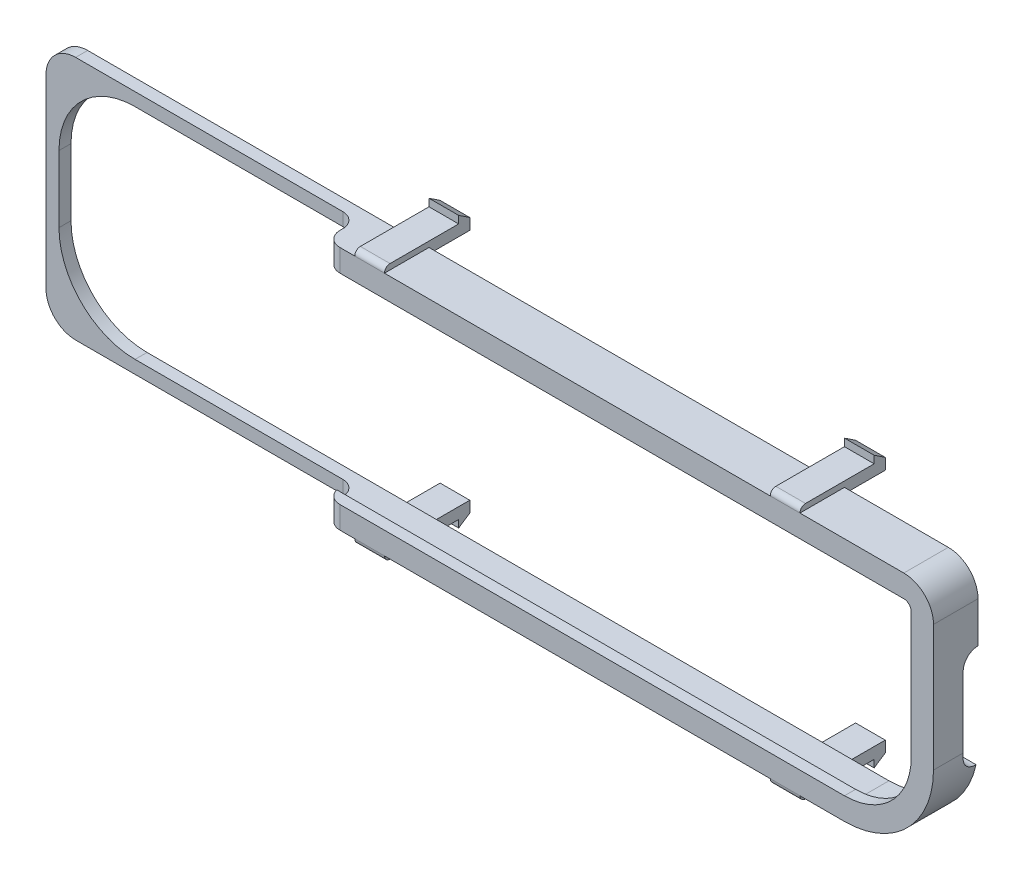
SolidWorks part; units mm, degrees
ref_plane "Front" through (0, 0, 0) normal (0, 0, 1) x (1, 0, 0)
ref_plane "Top" through (0, 0, 0) normal (0, 1, 0) x (1, 0, 0)
ref_plane "Right" through (0, 0, 0) normal (1, 0, 0) x (0, 0, -1)
ref_plane "Plane1 - PCB bottom plane" through (0, 0, 0) normal (0, 0, 1) x (1, 0, 0)
sketch "Sketch2 - footprint" plane through (0, 0, 0) normal (0, 0, 1) x (1, 0, 0)
  line L1 (10, 14.5) -> (118, 14.5) construction
  line L2 (0, 4.5) -> (0, -4.5) construction
  line L3 (10, -14.5) -> (110, -14.5) construction
  line L4 (120, 12.5) -> (120, -4.5) construction
  arc A0 (110, -14.5) -> (120, -4.5) centre (110, -4.5) ccw construction
  arc A1 (120, 12.5) -> (118, 14.5) centre (118, 12.5) ccw construction
  arc A2 (10, -14.5) -> (0, -4.5) centre (10, -4.5) cw construction
  arc A3 (10, 14.5) -> (0, 4.5) centre (10, 4.5) ccw construction
  point P4 (0, 0)
  point P10 (120, 14.5)
  point P13 (0, -14.5)
  point P16 (0, 14.5)
  dimension "D3" = 10
  dimension "D4" = 2
  dimension "D1" = 29
  dimension "D2" = 120
sketch "Sketch3" plane through (0, 0, 0) normal (0, 0, 1) x (1, 0, 0)
  line L33 (118, 14.75) -> (10, 14.75)
  line L34 (120.25, -4.5) -> (120.25, 12.5)
  line L35 (10, -14.75) -> (110, -14.75)
  line L36 (-0.25, 4.5) -> (-0.25, -4.5)
  line L37 (118, 14.75) -> (10, 14.75)
  line L38 (120.25, -4.5) -> (120.25, 12.5)
  line L39 (10, -14.75) -> (110, -14.75)
  line L40 (-0.25, 4.5) -> (-0.25, -4.5)
  line L45 (122, -4.5) -> (122, 12.5)
  line L46 (10, -16.5) -> (110, -16.5)
  line L47 (-2, 4.5) -> (-2, -4.5)
  line L48 (118, 16.5) -> (10, 16.5)
  line L49 (122, -4.5) -> (122, 12.5)
  line L50 (10, -16.5) -> (110, -16.5)
  line L51 (-2, 4.5) -> (-2, -4.5)
  line L52 (118, 16.5) -> (10, 16.5)
  arc A33 (120.25, 12.5) -> (118, 14.75) centre (118, 12.5) ccw
  arc A34 (110, -14.75) -> (120.25, -4.5) centre (110, -4.5) ccw
  arc A35 (-0.25, -4.5) -> (10, -14.75) centre (10, -4.5) ccw
  arc A36 (10, 14.75) -> (-0.25, 4.5) centre (10, 4.5) ccw
  arc A37 (120.25, 12.5) -> (118, 14.75) centre (118, 12.5) ccw
  arc A38 (110, -14.75) -> (120.25, -4.5) centre (110, -4.5) ccw
  arc A39 (-0.25, -4.5) -> (10, -14.75) centre (10, -4.5) ccw
  arc A40 (10, 14.75) -> (-0.25, 4.5) centre (10, 4.5) ccw
  arc A45 (122, 12.5) -> (118, 16.5) centre (118, 12.5) ccw
  arc A46 (110, -16.5) -> (122, -4.5) centre (110, -4.5) ccw
  arc A47 (-2, -4.5) -> (10, -16.5) centre (10, -4.5) ccw
  arc A48 (10, 16.5) -> (-2, 4.5) centre (10, 4.5) ccw
  arc A49 (122, 12.5) -> (118, 16.5) centre (118, 12.5) ccw
  arc A50 (110, -16.5) -> (122, -4.5) centre (110, -4.5) ccw
  arc A51 (-2, -4.5) -> (10, -16.5) centre (10, -4.5) ccw
  arc A52 (10, 16.5) -> (-2, 4.5) centre (10, 4.5) ccw
  dimension "D1" = 0.25
  dimension "D2" = 2
extrude "Boss-Extrude2 - thickness of TC + PCB" add sketch "Sketch3" along normal blind 4.5
sketch "Sketch4" plane through (0, 0, 4.5) normal (0, 0, 1) x (1, 0, 0)
  line L0 (40, 14.5) -> (118, 14.5) construction
  line L1 (10, 14.5) -> (118, 14.5) construction
  line L2 (40, -14.5) -> (110, -14.5) construction
  line L3 (10, -14.5) -> (110, -14.5) construction
  line L4 (120, 12.5) -> (120, -4.5) construction
  line L5 (120, 12.5) -> (120, -4.5) construction
  line L6 (40, 13.5) -> (118, 13.5)
  line L7 (119, 12.5) -> (119, -4.5)
  line L8 (40, -13.5) -> (110, -13.5)
  line L9 (40, 13.5) -> (40, 16.5)
  line L10 (118, 16.5) -> (10, 16.5) construction
  line L11 (40, 16.5) -> (118, 16.5)
  line L12 (40, -13.5) -> (40, -16.5)
  line L13 (10, -16.5) -> (110, -16.5) construction
  line L14 (40, -16.5) -> (110, -16.5)
  line L15 (122, -4.5) -> (122, 12.5) construction
  line L16 (122, -4.5) -> (122, 12.5)
  arc A0 (110, -14.5) -> (120, -4.5) centre (110, -4.5) ccw construction
  arc A1 (120, 12.5) -> (118, 14.5) centre (118, 12.5) ccw construction
  arc A2 (110, -14.5) -> (120, -4.5) centre (110, -4.5) ccw construction
  arc A3 (120, 12.5) -> (118, 14.5) centre (118, 12.5) ccw construction
  arc A4 (119, 12.5) -> (118, 13.5) centre (118, 12.5) ccw
  arc A5 (110, -13.5) -> (119, -4.5) centre (110, -4.5) ccw
  arc A6 (110, -16.5) -> (122, -4.5) centre (110, -4.5) ccw construction
  arc A7 (122, 12.5) -> (118, 16.5) centre (118, 12.5) ccw construction
  arc A8 (110, -16.5) -> (122, -4.5) centre (110, -4.5) ccw
  arc A9 (122, 12.5) -> (118, 16.5) centre (118, 12.5) ccw
  dimension "D1" = 80
  dimension "D2" = 1
extrude "Boss-Extrude3 - retaining top" add sketch "Sketch4" along normal blind 1.5
sketch "Sketch5" plane through (0, 0, 4.5) normal (0, 0, 1) x (1, 0, 0)
  line L8 (40, -16.5) -> (40, -14.75)
  line L9 (40, -14.75) -> (10, -14.75)
  line L10 (-0.25, -4.5) -> (-0.25, 4.5)
  line L11 (10, 14.75) -> (40, 14.75)
  line L12 (40, 14.75) -> (40, 16.5)
  line L13 (40, 16.5) -> (10, 16.5)
  line L14 (-2, 4.5) -> (-2, -4.5)
  line L15 (10, -16.5) -> (40, -16.5)
  line L16 (40, -16.5) -> (40, -14.75)
  line L17 (40, -14.75) -> (10, -14.75)
  line L18 (-0.25, -4.5) -> (-0.25, 4.5)
  line L19 (10, 14.75) -> (40, 14.75)
  line L20 (40, 14.75) -> (40, 16.5)
  line L21 (40, 16.5) -> (10, 16.5)
  line L22 (-2, 4.5) -> (-2, -4.5)
  line L23 (10, -16.5) -> (40, -16.5)
  arc A4 (-0.25, -4.5) -> (10, -14.75) centre (10, -4.5) ccw
  arc A5 (10, 14.75) -> (-0.25, 4.5) centre (10, 4.5) ccw
  arc A6 (10, 16.5) -> (-2, 4.5) centre (10, 4.5) ccw
  arc A7 (-2, -4.5) -> (10, -16.5) centre (10, -4.5) ccw
  arc A8 (-0.25, -4.5) -> (10, -14.75) centre (10, -4.5) ccw
  arc A9 (10, 14.75) -> (-0.25, 4.5) centre (10, 4.5) ccw
  arc A10 (10, 16.5) -> (-2, 4.5) centre (10, 4.5) ccw
  arc A11 (-2, -4.5) -> (10, -16.5) centre (10, -4.5) ccw
  dimension "D1" = 0
extrude "Cut-Extrude1 - exposed TC front" cut sketch "Sketch5" against normal blind 2.881
fillet "Fillet1" radius 2 4 edges at (40, 15, 6) (40, 15.625, 1.619) (40, -15, 6) (40, -15.625, 1.619)
sketch "Sketch6" plane through (0, 0, 1.619) normal (0, 0, 1) x (1, 0, 0)
  line L0 (-0.25, -4.5) -> (-0.25, 4.5) construction
  line L1 (-0.25, 3) -> (-2, 3)
  line L2 (-0.25, 3) -> (-0.25, -3)
  line L3 (-0.25, -3) -> (-2, -3)
  line L4 (-2, 3) -> (-2, -3)
  line L5 (-2, 4.5) -> (-2, -4.5) construction
  point P9 (-0.25, 0)
  dimension "D1" = 6
extrude "Boss-Extrude4 - front lip" [suppressed] add sketch "Sketch6" along normal blind 1
fillet "Fillet2" [suppressed] radius 1
sketch "Sketch7" plane through (122, 0, 0) normal (1, 0, 0) x (0, 0, -1)
  line L0 (0, -4.5) -> (0, 12.5) construction
  line L1 (0, -7) -> (-2, -7)
  line L2 (0, -7) -> (0, 7)
  line L3 (0, 7) -> (-2, 7)
  line L4 (-2, -7) -> (-2, 7)
  point P7 (0, 0)
  dimension "D1" = 14
  dimension "D2" = 2
extrude "Cut-Extrude1 - USBC cutout" cut sketch "Sketch7" against normal blind 5
fillet "Fillet3" radius 2 2 edges at (121.125, 7, 2) (120.8386, -7, 2)
sketch "Sketch8" plane through (0, 0, 0) normal (0, 0, -1) x (-1, 0, 0)
  line L0 (-10, -14.75) -> (-110, -14.75) construction
  line L1 (-44, -15.75) -> (-48, -15.75)
  line L2 (-44, -15.75) -> (-44, -17.25)
  line L3 (-44, -17.25) -> (-48, -17.25)
  line L4 (-48, -15.75) -> (-48, -17.25)
  line L6 (-100, -15.75) -> (-104, -15.75)
  line L7 (-100, -15.75) -> (-100, -17.25)
  line L8 (-100, -17.25) -> (-104, -17.25)
  line L9 (-104, -15.75) -> (-104, -17.25)
  point P13 (-46, -17.25)
  point P14 (-102, -17.25)
  dimension "D1" = 1.5
  dimension "D2" = 4
  dimension "D3" = 46
  dimension "D4" = 102
  dimension "D5" = 1
extrude "Boss-Extrude5 - snap posts" add sketch "Sketch8" along normal blind 5.5
sketch "Sketch9" plane through (44, 0, 0) normal (-1, 0, 0) x (0, 0, 1)
  line L0 (-5.5, -17.25) -> (-4, -18.25)
  line L1 (-4, -18.25) -> (-4, -17.25)
  line L2 (-5.5, -17.25) -> (0, -17.25) construction
  line L3 (-4, -17.25) -> (-5.5, -17.25)
  dimension "D1" = 1
  dimension "D2" = 1.5
extrude "Boss-Extrude6 - snap notch 1" add sketch "Sketch9" against normal up to surface (4 mm away) up to face at (48, -16.5, -2.2)
sketch "Sketch10" plane through (100, 0, 0) normal (-1, 0, 0) x (0, 0, 1)
  line L0 (-5.5, -17.25) -> (-4, -18.25) construction
  line L1 (-4, -18.25) -> (-4, -17.25) construction
  line L2 (-4, -18.25) -> (-4, -17.25)
  line L3 (-5.5, -17.25) -> (-4, -18.25)
  line L4 (-4, -17.25) -> (-5.5, -17.25)
extrude "Boss-Extrude7 - snap notch 2" add sketch "Sketch10" against normal up to surface (4 mm away) up to face at (104, -16.5, -2.2)
sketch "Sketch11" plane through (0, 0, 0) normal (0, 0, -1) x (-1, 0, 0)
  line L1 (-44, -17.25) -> (-48, -17.25)
  line L2 (-44, -17.25) -> (-44, -14.75)
  line L3 (-44, -14.75) -> (-48, -14.75)
  line L4 (-48, -17.25) -> (-48, -14.75)
  line L7 (-10, -14.75) -> (-110, -14.75) construction
  line L9 (-35.984, -18.7414) -> (-36.1672, -18.7414) construction
  line L10 (-44, -15.75) -> (-48, -15.75) construction
  line L12 (-100, -15.75) -> (-104, -15.75) construction
  line L13 (-100, -17.25) -> (-104, -17.25)
  line L14 (-100, -17.25) -> (-100, -14.75)
  line L15 (-100, -14.75) -> (-104, -14.75)
  line L16 (-104, -17.25) -> (-104, -14.75)
  point P6 (-46, -15.75)
  point P7 (-46, -14.75)
  point P27 (-102, -15.75)
  point P28 (-102, -14.75)
extrude "Boss-Extrude1 - snap bumps" add sketch "Sketch11" against normal blind 6
mirror "Mirror1" about plane through (0, 0, 0) normal (0, 1, 0) of "Boss-Extrude1 - snap bumps", "Boss-Extrude5 - snap posts", "Boss-Extrude6 - snap notch 1", "Boss-Extrude7 - snap notch 2"
fillet "Fillet6" radius 1 4 edges at (46, -15.75, 0) (102, -15.75, 0) (102, 15.75, 0) (46, 15.75, 0)
fillet "Fillet7" radius 0.75 4 edges at (102, -17.25, 6) (46, -17.25, 6) (46, 17.25, 6) (102, 17.25, 6)
sketch "Sketch13" plane through (0, 0, 1.619) normal (0, 0, 1) x (1, 0, 0)
  line L0 (-2, 4.5) -> (-2, 16.5)
  line L1 (-2, 16.5) -> (10, 16.5)
  line L2 (-2, -4.5) -> (-2, -16.5)
  line L3 (-2, -16.5) -> (10, -16.5)
  arc A0 (-2, -4.5) -> (10, -16.5) centre (10, -4.5) ccw construction
  arc A1 (10, 16.5) -> (-2, 4.5) centre (10, 4.5) ccw construction
  arc A2 (-2, -4.5) -> (10, -16.5) centre (10, -4.5) ccw
  arc A3 (10, 16.5) -> (-2, 4.5) centre (10, 4.5) ccw
extrude "Boss-Extrude1" add sketch "Sketch13" against normal up to surface (1.619 mm away) up to face at (16.857, 0, 0)
fillet "Fillet8" radius 4 2 edges at (-2, 16.5, 0.8095) (-2, -16.5, 0.8095)
